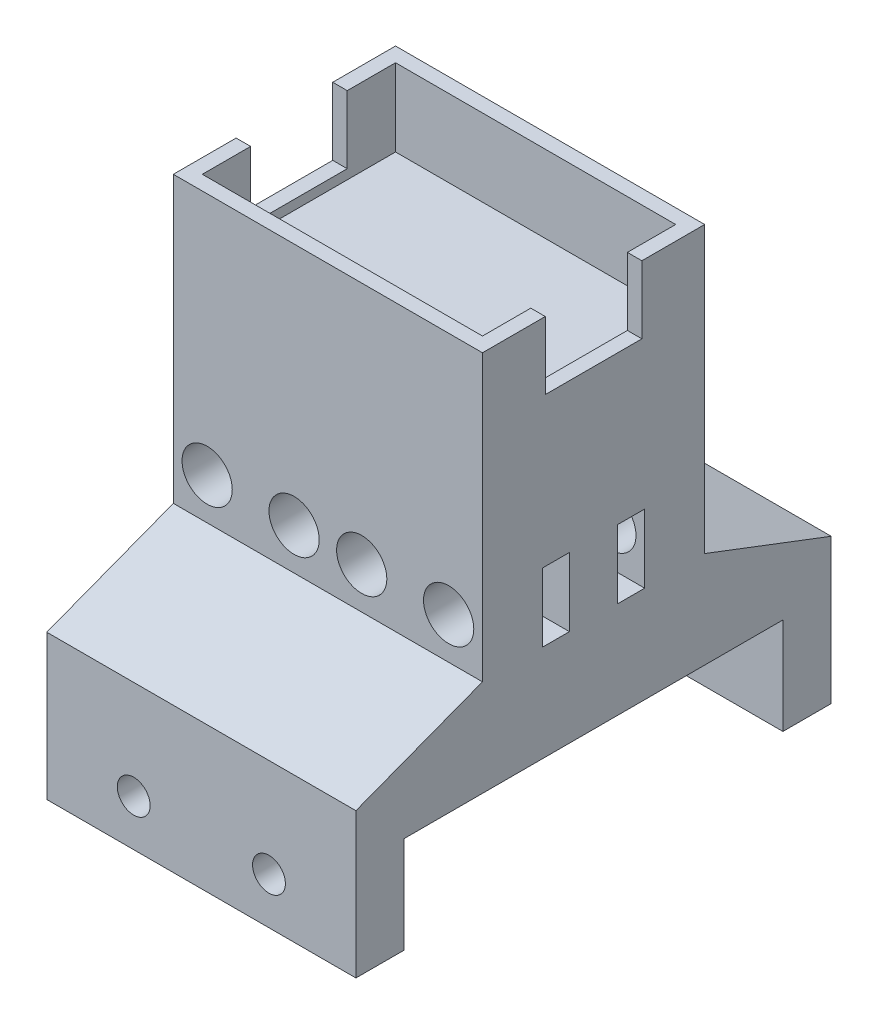
SolidWorks part; units mm, degrees
ref_plane "Front Plane" through (0, 0, 0) normal (0, 0, 1) x (1, 0, 0)
ref_plane "Top Plane" through (0, 0, 0) normal (0, 1, 0) x (1, 0, 0)
ref_plane "Right Plane" through (0, 0, 0) normal (1, 0, 0) x (0, 0, -1)
sketch "Sketch4" plane through (0, 0, 0) normal (0, 1, 0) x (1, 0, 0)
  line L1 (-16, -11.5) -> (16, -11.5)
  line L2 (-16, -11.5) -> (-16, 11.5)
  line L3 (-16, 11.5) -> (16, 11.5)
  line L4 (16, -11.5) -> (16, 11.5)
  line L5 (-16, -11.5) -> (16, 11.5) construction
  line L6 (-16, 11.5) -> (16, -11.5) construction
  point P0 (0, 0)
  dimension "D1" = 32
  dimension "D2" = 23
extrude "Boss-Extrude3" add sketch "Sketch4" along normal blind 19.5
sketch "Sketch5" plane through (0, 19.5, 0) normal (0, 1, 0) x (1, 0, 0)
  line L1 (-14.5, -10) -> (14.5, -10)
  line L2 (-14.5, -10) -> (-14.5, 10)
  line L3 (-14.5, 10) -> (14.5, 10)
  line L4 (14.5, -10) -> (14.5, 10)
  line L5 (-14.5, -10) -> (14.5, 10) construction
  line L6 (-14.5, 10) -> (14.5, -10) construction
  point P0 (0, 0)
  dimension "D1" = 29
  dimension "D2" = 20
extrude "Cut-Extrude2" cut sketch "Sketch5" against normal blind 8
sketch "Sketch7" plane through (16, 0, 0) normal (1, 0, 0) x (0, 0, -1)
  line L1 (-5, 12.5) -> (5, 12.5)
  line L2 (-5, 12.5) -> (-5, 19.5)
  line L3 (-5, 19.5) -> (5, 19.5)
  line L4 (5, 12.5) -> (5, 19.5)
  line L5 (-11.5, 19.5) -> (11.5, 19.5) construction
  point P6 (0, 19.5)
  point P8 (0, 19.5)
  dimension "D1" = 10
  dimension "D2" = 7
extrude "Cut-Extrude4" cut sketch "Sketch7" against normal through all
sketch "Sketch8" plane through (0, 0, 0) normal (0, -1, 0) x (-1, 0, 0)
  line L17 (-16, -11.5) -> (16, -11.5)
  line L18 (-16, -11.5) -> (-16, 11.5)
  line L19 (-16, 11.5) -> (16, 11.5)
  line L20 (16, -11.5) -> (16, 11.5)
  line L21 (-16, -11.5) -> (16, 11.5) construction
  line L22 (-16, 11.5) -> (16, -11.5) construction
  point P4 (0, 0)
extrude "Boss-Extrude4" add sketch "Sketch8" along normal blind 10
ref_plane "Plane1" through (0, 0, 0) normal (0, 0, -1) x (-1, 0, 0)
sketch "Sketch12" plane through (0, 0, -11.5) normal (0, 0, -1) x (-1, 0, 0)
  line L0 (0, 19.5) -> (0, -10) construction
  line L1 (-16, 19.5) -> (16, 19.5) construction
  line L2 (16, -10) -> (-16, -10) construction
  line L3 (-16, 19.5) -> (0, -10) construction
  line L4 (0, 19.5) -> (-16, -10) construction
  line L5 (-8, 4.75) -> (-8, -10) construction
  line L6 (-16, 19.5) -> (-16, -10) construction
  circle A0 centre (-12.5, -5.7269) radius 2.6
  circle A1 centre (-3.5, -5.7269) radius 2.6
  circle A2 centre (3.5, -5.7269) radius 2.6
  circle A3 centre (12.5, -5.7269) radius 2.6
  dimension "D1" = 5.2
  dimension "D3" = 3.5
  dimension "D2" = 4.2731
extrude "Cut-Extrude5" cut sketch "Sketch12" against normal blind 7
pattern_circular "CirPattern1" count 2 over 180 about axis through (0, 11.5, 0) along (0, 1, 0) of "Cut-Extrude5"
sketch "Sketch13" plane through (0, -10, 0) normal (0, -1, 0) x (-1, 0, 0)
  line L0 (16, -11.5) -> (16, 11.5) construction
  line L1 (16, 2.5) -> (1, 2.5)
  line L2 (16, 2.5) -> (16, 5.2916)
  line L3 (16, 5.2916) -> (1, 5.2916)
  line L4 (1, 2.5) -> (1, 5.2916)
  line L5 (16, 2.5) -> (1, 5.2916) construction
  line L6 (16, 5.2916) -> (1, 2.5) construction
  line L7 (13.475, 0) -> (-13.475, 0) construction
  line L8 (0, -11.5) -> (0, 11.5) construction
  line L9 (-16, -11.5) -> (16, -11.5) construction
  line L10 (16, 11.5) -> (-16, 11.5) construction
  line L11 (-16, 5.2916) -> (-1, 5.2916)
  line L12 (-1, 2.5) -> (-1, 5.2916)
  line L13 (-16, 2.5) -> (-1, 2.5)
  line L14 (-16, 2.5) -> (-16, 5.2916)
  line L15 (-16, -2.5) -> (-16, -5.2916)
  line L16 (-16, -2.5) -> (-1, -2.5)
  line L17 (-1, -2.5) -> (-1, -5.2916)
  line L18 (-16, -5.2916) -> (-1, -5.2916)
  line L19 (16, -5.2916) -> (1, -5.2916)
  line L20 (1, -2.5) -> (1, -5.2916)
  line L21 (16, -2.5) -> (1, -2.5)
  line L22 (16, -2.5) -> (16, -5.2916)
  point P4 (8.5, 3.8958)
  dimension "D1" = 15
  dimension "D2" = 2.7916
  dimension "D3" = 2.5
extrude "Cut-Extrude6" cut sketch "Sketch13" against normal blind 7.1
sketch "Sketch14" plane through (0, -10, 0) normal (0, -1, 0) x (-1, 0, 0)
  line L1 (16, 11.5) -> (-16, 11.5)
  line L2 (16, 11.5) -> (16, -11.5)
  line L3 (16, -11.5) -> (-16, -11.5)
  line L4 (-16, 11.5) -> (-16, -11.5)
  line L5 (16, 11.5) -> (-16, -11.5) construction
  line L6 (16, -11.5) -> (-16, 11.5) construction
  point P4 (0, 0)
extrude "Boss-Extrude5" add sketch "Sketch14" along normal blind 5
sketch "Sketch15" plane through (-16, 0, 0) normal (-1, 0, 0) x (0, 0, 1)
  line L1 (-24.6, -15) -> (-24.6, -30)
  line L2 (-24.6, -30) -> (-19.6, -30)
  line L3 (-19.6, -30) -> (-19.6, -20)
  line L4 (-19.6, -20) -> (19.6, -20)
  line L5 (0, -20) -> (0, -15) construction
  line L6 (11.5, -15) -> (-11.5, -15) construction
  line L8 (19.6, -30) -> (19.6, -20)
  line L9 (24.6, -30) -> (19.6, -30)
  line L10 (24.6, -15) -> (24.6, -30)
  line L12 (-24.6, -15) -> (-11.5, -10)
  line L13 (-11.5, 19.5) -> (-11.5, -15) construction
  line L14 (-11.5, -10) -> (-11.5, -15)
  line L15 (-11.5, -15) -> (11.5, -15)
  line L16 (11.5, -10) -> (11.5, -15)
  line L17 (24.6, -15) -> (11.5, -10)
  dimension "D1" = 39.2
  dimension "D2" = 10
  dimension "D3" = 5
  dimension "D4" = 5
extrude "Boss-Extrude6" add sketch "Sketch15" against normal up to surface (32 mm away) up to face at (16, -6.45, -3.8958)
sketch "Sketch16" plane through (0, 0, -24.6) normal (0, 0, -1) x (-1, 0, 0)
  line L0 (0, 0) -> (0, 50000) construction
  line L1 (-16, -20) -> (16, -20) construction
  circle A0 centre (7, -25.2) radius 1.7
  circle A1 centre (-7, -25.2) radius 1.7
  dimension "D1" = 3.4
  dimension "D2" = 7
  dimension "D3" = 5.2
extrude "Cut-Extrude7" cut sketch "Sketch16" against normal through all
